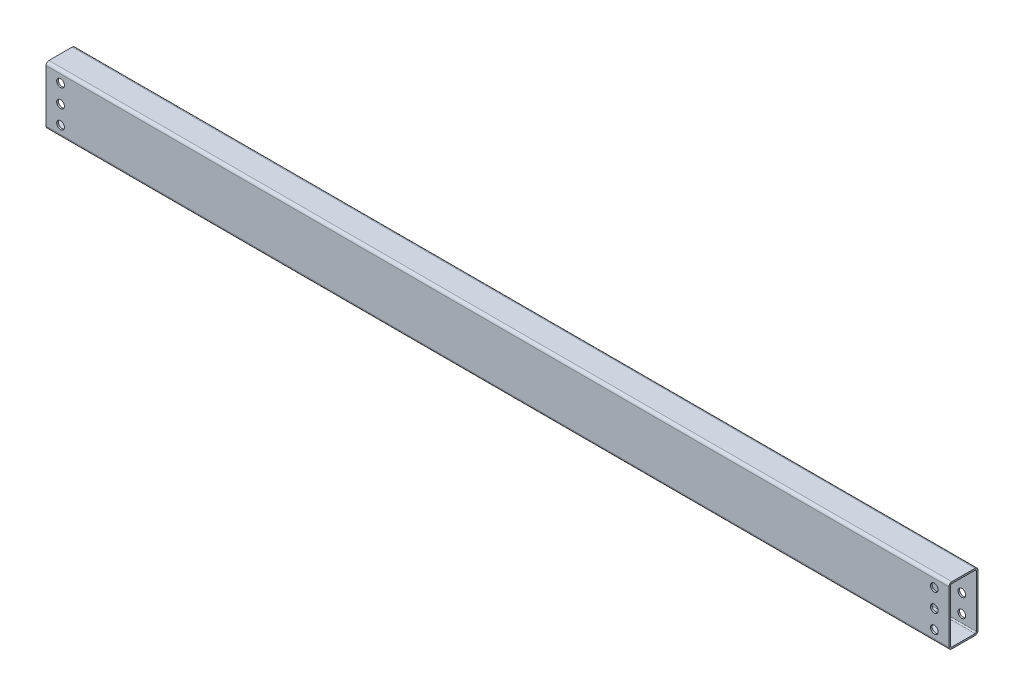
SolidWorks part; units mm, degrees
material "6061-T6 (SS)"
ref_plane "Front" through (0, 0, 0) normal (0, 0, 1) x (1, 0, 0)
ref_plane "Top" through (0, 0, 0) normal (0, 1, 0) x (1, 0, 0)
ref_plane "Right" through (0, 0, 0) normal (1, 0, 0) x (0, 0, -1)
sketch "Sketch1" plane through (0, 0, 0) normal (1, 0, 0) x (0, 0, -1)
  line L0 (10.16, -25.4) -> (-10.16, -25.4)
  line L1 (12.7, -22.86) -> (12.7, 22.86)
  line L2 (10.16, 25.4) -> (-10.16, 25.4)
  line L3 (-12.7, -22.86) -> (-12.7, 22.86)
  line L4 (12.7, -25.4) -> (-12.7, 25.4) construction
  line L5 (12.7, 25.4) -> (-12.7, -25.4) construction
  arc A0 (-10.16, -25.4) -> (-12.7, -22.86) centre (-10.16, -22.86) cw
  arc A1 (10.16, -25.4) -> (12.7, -22.86) centre (10.16, -22.86) ccw
  arc A2 (12.7, 22.86) -> (10.16, 25.4) centre (10.16, 22.86) ccw
  arc A3 (-10.16, 25.4) -> (-12.7, 22.86) centre (-10.16, 22.86) ccw
  point P0 (0, 0)
  dimension "D3" = 2.54
  dimension "D1" = 25.4
  dimension "D2" = 50.8
extrude "Extrude-Thin1" add sketch "Sketch1" along normal mid plane 787.4 thin thin type one direction reverse wall 1.4478
hole_wizard "1/4 Clearance Hole1" positions "Sketch2" profile "Sketch3" hole size "1/4" standard "ANSI Inch" end condition through all
sketch "Sketch2" plane through (0, 0, -12.7) normal (0, 0, -1) x (-1, 0, 0)
  line L0 (-393.7, -22.86) -> (-393.7, 22.86) construction
  line L1 (-393.7, 25.4) -> (393.7, 25.4) construction
  line L2 (-393.7, -25.4) -> (393.7, -25.4) construction
  line L3 (-381, 15.875) -> (-381, -15.875) construction
  line L4 (0, 0) -> (0, -37.3791) construction
  point P0 (-381, 15.875)
  point P2 (-381, -15.875)
  point P15 (-381, 0)
  point P23 (381, -15.875)
  point P24 (381, 0)
  point P25 (381, 15.875)
  dimension "D1" = 12.7
  dimension "D2" = 9.525
  dimension "D3" = 9.525
sketch "Sketch3" plane through (381, 15.875, -12.7) normal (1, 0, 0) x (0, 1, 0)
  line L0 (0, 0) -> (0, 25.4)
  line L1 (0, 25.4) -> (3.3782, 25.4)
  line L2 (3.3782, 25.4) -> (3.3782, 0)
  line L5 (3.3782, 0) -> (0, 0)
  line L11 (0, -6.35) -> (0, 107.95) construction
  dimension "Thru Hole Dia." = 6.7564
  dimension "Thru Hole Depth" = 25.4
hole_wizard "1/4 Clearance Hole2" positions "Sketch4" profile "Sketch5" hole size "1/4" standard "ANSI Inch" end condition up to next
sketch "Sketch4" plane through (0, 0, -12.7) normal (0, 0, -1) x (-1, 0, 0)
  line L0 (-234.95, 15.875) -> (-234.95, -15.875) construction
  line L2 (-393.7, 25.4) -> (393.7, 25.4) construction
  line L3 (-393.7, -25.4) -> (393.7, -25.4) construction
  line L4 (0, 0) -> (0, -51.4899) construction
  point P19 (-234.95, 15.875)
  point P21 (-234.95, 0)
  point P23 (-234.95, -15.875)
  point P42 (234.95, -15.875)
  point P43 (234.95, 0)
  point P44 (234.95, 15.875)
  dimension "D1" = 9.525
  dimension "D2" = 9.525
  dimension "D3" = 469.9
sketch "Sketch5" plane through (234.95, 15.875, -12.7) normal (1, 0, 0) x (0, 1, 0)
  line L0 (0, 0) -> (0, 1.4478)
  line L1 (0, 1.4478) -> (3.3782, 1.4478)
  line L2 (3.3782, 1.4478) -> (3.3782, 0)
  line L5 (3.3782, 0) -> (0, 0)
  line L11 (0, -6.35) -> (0, 107.95) construction
  dimension "Thru Hole Dia." = 6.7564
  dimension "Thru Hole Depth" = 1.4478
sketch "Sketch6" plane through (0, 0, -12.7) normal (0, 0, -1) x (-1, 0, 0)
  line L0 (-393.7, -25.4) -> (393.7, -25.4) construction
  line L2 (-130.175, -25.4) -> (-117.475, -25.4)
  line L3 (-130.175, -25.4) -> (-130.175, -9.525)
  line L4 (-127, -6.35) -> (-120.65, -6.35)
  line L5 (-117.475, -25.4) -> (-117.475, -9.525)
  line L6 (-47.625, -25.4) -> (-34.925, -25.4)
  line L11 (-47.625, -25.4) -> (-47.625, -9.525)
  line L12 (-44.45, -6.35) -> (-38.1, -6.35)
  line L13 (-34.925, -25.4) -> (-34.925, -9.525)
  line L14 (34.925, -25.4) -> (47.625, -25.4)
  line L15 (34.925, -25.4) -> (34.925, -9.525)
  line L16 (38.1, -6.35) -> (44.45, -6.35)
  line L17 (47.625, -25.4) -> (47.625, -9.525)
  line L18 (117.475, -25.4) -> (130.175, -25.4)
  line L19 (117.475, -25.4) -> (117.475, -9.525)
  line L20 (120.65, -6.35) -> (127, -6.35)
  line L21 (130.175, -25.4) -> (130.175, -9.525)
  line L22 (0, 0) -> (0, -9.525) construction
  arc A0 (-120.65, -6.35) -> (-117.475, -9.525) centre (-120.65, -9.525) cw
  arc A1 (-130.175, -9.525) -> (-127, -6.35) centre (-127, -9.525) cw
  arc A4 (-38.1, -6.35) -> (-34.925, -9.525) centre (-38.1, -9.525) cw
  arc A5 (-47.625, -9.525) -> (-44.45, -6.35) centre (-44.45, -9.525) cw
  arc A6 (44.45, -6.35) -> (47.625, -9.525) centre (44.45, -9.525) cw
  arc A7 (34.925, -9.525) -> (38.1, -6.35) centre (38.1, -9.525) cw
  arc A8 (127, -6.35) -> (130.175, -9.525) centre (127, -9.525) cw
  arc A9 (117.475, -9.525) -> (120.65, -6.35) centre (120.65, -9.525) cw
  dimension "D1" = 3.175
  dimension "D2" = 12.7
  dimension "D3" = 19.05
  dimension "D5" = 82.55
  dimension "D4" = 4
extrude "Cut-Extrude1" cut sketch "Sketch6" against normal blind 9.525
